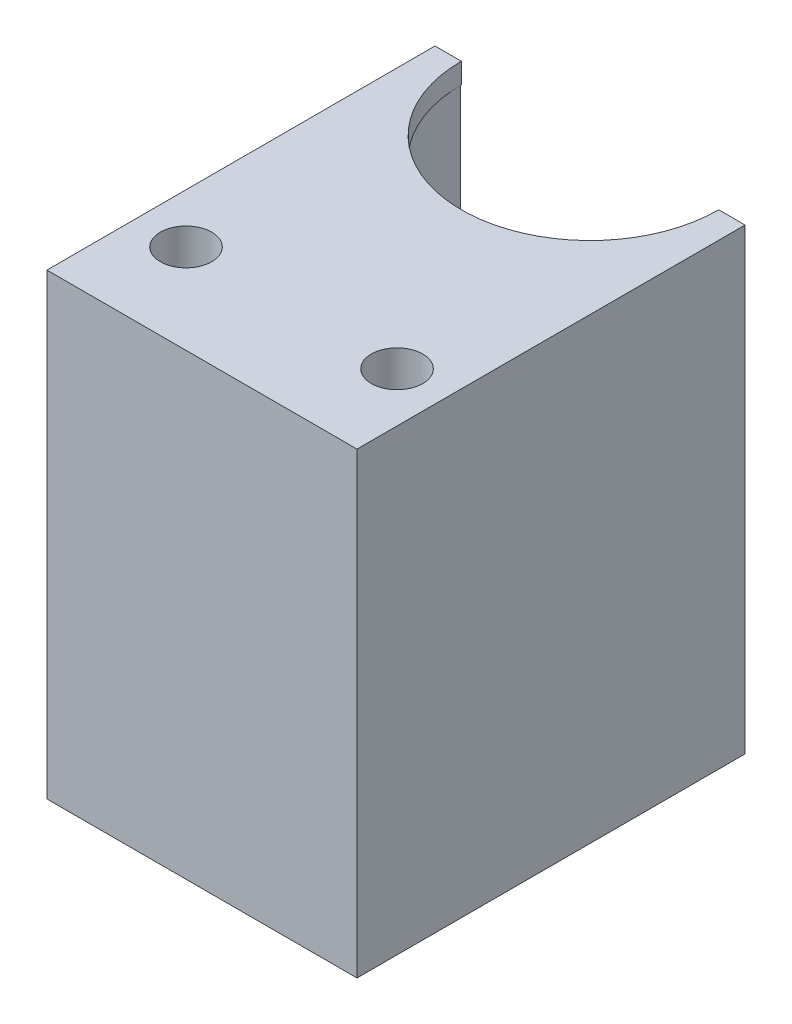
SolidWorks part; units mm, degrees
ref_plane "Front Plane" through (0, 0, 0) normal (0, 0, 1) x (1, 0, 0)
ref_plane "Top Plane" through (0, 0, 0) normal (0, 1, 0) x (1, 0, 0)
ref_plane "Right Plane" through (0, 0, 0) normal (1, 0, 0) x (0, 0, -1)
sketch "Sketch2" plane through (0, 0, 0) normal (0, 1, 0) x (1, 0, 0)
  line L0 (15.061, 0) -> (15.061, 37.7)
  line L1 (-12.561, 2.5) -> (12.561, 2.5)
  line L2 (-12.561, 2.5) -> (-12.561, 37.7)
  line L4 (12.561, 2.5) -> (12.561, 37.7)
  line L5 (15.061, 37.7) -> (12.561, 37.7)
  line L7 (-15.061, 37.7) -> (-15.061, 0)
  line L8 (-15.061, 0) -> (15.061, 0)
  line L10 (-15.061, 37.7) -> (-12.561, 37.7)
  point P4 (0, 2.5)
  point P12 (0, 0)
  dimension "D1" = 2.5
  dimension "D2" = 2.5
  dimension "D3" = 37.7
  dimension "D4" = 25.122
  dimension "D5" = 15.061
extrude "Boss-Extrude1" add sketch "Sketch2" along normal blind 32.5
sketch "Sketch4" plane through (0, 0, 0) normal (0, -1, 0) x (1, 0, 0)
  line L0 (-15.061, 0) -> (-15.061, -7.4438)
  line L8 (15.061, -7.4438) -> (15.061, 0)
  line L9 (15.061, 0) -> (-15.061, 0)
  line L10 (15.061, 0) -> (15.061, -37.7) construction
  line L13 (-15.061, -7.4438) -> (-15.061, -37.7)
  line L23 (-15.061, -37.7) -> (-12.561, -37.7)
  line L34 (-12.561, -37.7) -> (-12.561, -7.5)
  line L35 (-12.561, -2.5) -> (-12.561, -37.7) construction
  line L36 (-12.561, -7.5) -> (12.561, -7.5)
  line L37 (12.561, -37.7) -> (12.561, -2.5) construction
  line L38 (12.561, -7.5) -> (12.561, -37.7)
  line L39 (12.561, -37.7) -> (15.061, -37.7)
  line L40 (15.061, -37.7) -> (15.061, -7.4438)
  circle A2 centre (-10.2499, -4.95) radius 1.05
  circle A5 centre (10.2499, -4.95) radius 1.05
  dimension "D5" = 2.1
  dimension "D1" = 7.5
  dimension "D6" = 4.8111
  dimension "D7" = 4.95
  dimension "D8" = 4.8111
extrude "Boss-Extrude2" add sketch "Sketch4" along normal blind 2
sketch "Sketch7" plane through (0, -2, 0) normal (0, -1, 0) x (1, 0, 0)
  line L0 (-15.061, 0) -> (-15.061, -37.7)
  line L1 (-15.061, -37.7) -> (-12.561, -37.7)
  line L2 (-15.061, 0) -> (15.061, 0)
  line L4 (15.061, 0) -> (15.061, -37.7)
  line L5 (15.061, -37.7) -> (12.561, -37.7)
  line L6 (12.561, -37.7) -> (12.561, -7.5)
  line L7 (12.561, -7.5) -> (-12.561, -7.5)
  line L8 (-12.561, -7.5) -> (-12.561, -37.7)
  circle A2 centre (-10.2499, -4.95) radius 2.495
  circle A3 centre (10.2499, -4.95) radius 2.495
  dimension "D1" = 4.99
extrude "Boss-Extrude5" add sketch "Sketch7" along normal blind 2
sketch "Sketch8" plane through (0, -4, 0) normal (0, -1, 0) x (1, 0, 0)
  line L0 (-15.061, 0) -> (-15.061, -37.7)
  line L1 (-15.061, -37.7) -> (15.061, -37.7)
  line L2 (15.061, -37.7) -> (15.061, 0) construction
  line L3 (12.561, -37.7) -> (15.061, -37.7) construction
  line L4 (-15.061, 0) -> (15.061, 0)
  line L6 (15.061, 0) -> (15.061, -37.7)
  circle A0 centre (-10.2499, -4.95) radius 2.495
  circle A1 centre (10.2499, -4.95) radius 2.495
  circle A2 centre (10.2499, -4.95) radius 2.495 construction
  circle A3 centre (-10.2499, -4.95) radius 2.495 construction
extrude "Boss-Extrude6" add sketch "Sketch8" along normal blind 2
sketch "Sketch5" plane through (0, 32.5, 0) normal (0, 1, 0) x (1, 0, 0)
  line L0 (-7.5, 10) -> (-7.5, 2.5)
  line L9 (12.561, 2.5) -> (-12.561, 2.5) construction
  line L11 (-10.2499, 12) -> (-7.5, 10)
  line L13 (-15.061, 0) -> (15.061, 0) construction
  line L15 (-15.061, 0) -> (-15.061, 37.7)
  line L17 (10.2499, 12) -> (7.5, 10)
  line L20 (15.061, 0) -> (15.061, 37.7)
  line L21 (-7.5, 2.5) -> (7.5, 2.5)
  line L22 (7.5, 2.5) -> (7.5, 10)
  line L23 (-15.061, 0) -> (15.061, 0)
  line L24 (-10.2499, 12) -> (-12.561, 12)
  line L25 (-12.561, 37.7) -> (-12.561, 7.5) construction
  line L26 (-12.561, 12) -> (-12.561, 37.7)
  line L27 (-12.561, 37.7) -> (-15.061, 37.7)
  line L30 (15.061, 37.7) -> (12.561, 37.7)
  line L31 (12.561, 37.7) -> (12.561, 12)
  line L32 (12.561, 7.5) -> (12.561, 37.7) construction
  line L33 (12.561, 12) -> (10.2499, 12)
  circle A0 centre (-10.2499, 4.95) radius 1.05 construction
  circle A1 centre (-10.2499, 8.7) radius 1.05
  circle A2 centre (10.2499, 8.7) radius 1.05
  dimension "D4" = 0
  dimension "D7" = 8.7
  dimension "D1" = 12
  dimension "D2" = 7.561
  dimension "D3" = 20.4998
  dimension "D5" = 10
  dimension "D6" = 7.561
extrude "Boss-Extrude3" add sketch "Sketch5" along normal blind 2
sketch "Sketch9" plane through (0, 34.5, 0) normal (0, 1, 0) x (1, 0, 0)
  line L0 (-15.061, 0) -> (-15.061, 37.7)
  line L1 (-15.061, 37.7) -> (-12.561, 37.7)
  line L2 (-12.561, 37.7) -> (-12.561, 12)
  line L3 (-12.561, 12) -> (-10.2499, 12)
  line L4 (-10.2499, 12) -> (-7.5, 10)
  line L5 (-7.5, 10) -> (-7.5, 2.5)
  line L6 (-7.5, 2.5) -> (7.5, 2.5)
  line L7 (7.5, 2.5) -> (7.5, 10)
  line L8 (7.5, 10) -> (10.2499, 12)
  line L9 (10.2499, 12) -> (7.5, 10) construction
  line L10 (10.2499, 12) -> (12.561, 12)
  line L11 (12.561, 7.5) -> (12.561, 37.7) construction
  line L12 (12.561, 12) -> (12.561, 37.7)
  line L13 (12.561, 37.7) -> (15.061, 37.7)
  line L14 (15.061, 0) -> (15.061, 37.7) construction
  line L15 (15.061, 37.7) -> (12.561, 37.7) construction
  line L16 (15.061, 37.7) -> (15.061, 0)
  line L17 (15.061, 0) -> (-15.061, 0)
  circle A0 centre (-10.2499, 8.7) radius 2.495
  circle A1 centre (10.2499, 8.7) radius 2.495
  dimension "D1" = 4.99
extrude "Boss-Extrude7" add sketch "Sketch9" along normal blind 2
sketch "Sketch10" plane through (0, 36.5, 0) normal (0, 1, 0) x (1, 0, 0)
  line L1 (-15.061, 37.7) -> (15.061, 37.7)
  line L2 (-15.061, 37.7) -> (-15.061, 0)
  line L3 (-15.061, 0) -> (15.061, 0)
  line L4 (15.061, 37.7) -> (15.061, 0)
  circle A0 centre (-10.2499, 8.7) radius 2.495
  circle A1 centre (10.2499, 8.7) radius 2.495
  circle A2 centre (-10.2499, 8.7) radius 2.495 construction
  circle A3 centre (10.2499, 8.7) radius 2.495 construction
extrude "Boss-Extrude8" add sketch "Sketch10" along normal blind 2
sketch "Sketch11" plane through (0, 38.5, 0) normal (0, 1, 0) x (1, 0, 0)
  line L0 (15.061, 37.7) -> (-15.061, 37.7) construction
  circle A0 centre (0, 37.7) radius 12.5
  dimension "D1" = 25
extrude "Cut-Extrude1" cut sketch "Sketch11" against normal through all
ref_plane "Box Mid Plane" through (0, 16.25, 0) normal (0, 1, 0) x (1, 0, 0)
